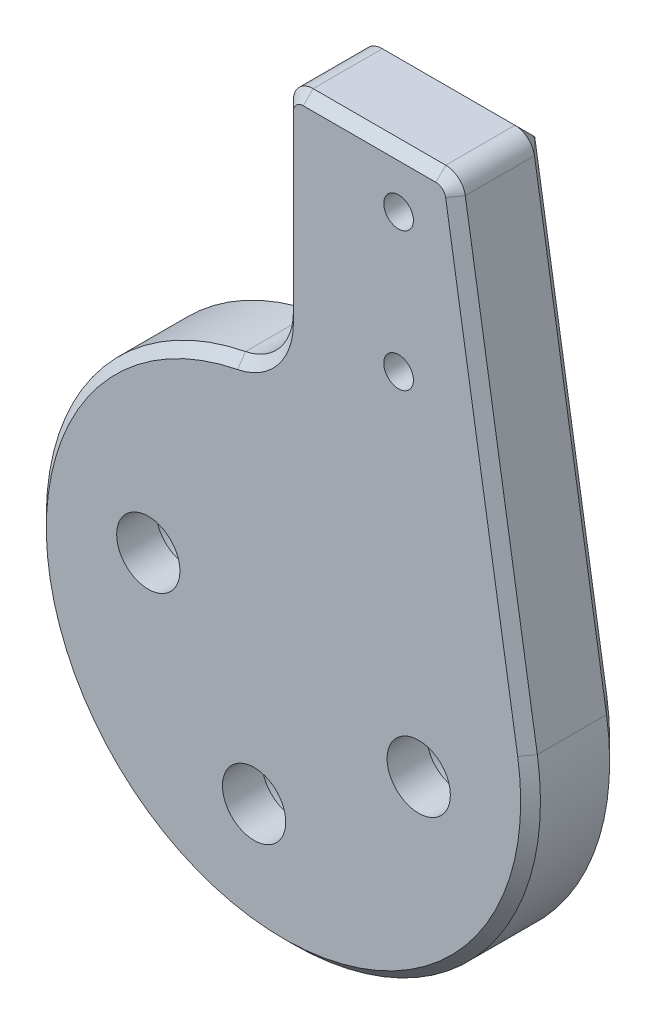
SolidWorks part; units mm, degrees
ref_plane "Front Plane" through (0, 0, 0) normal (0, 0, 1) x (1, 0, 0)
ref_plane "Top Plane" through (0, 0, 0) normal (0, 1, 0) x (1, 0, 0)
ref_plane "Right Plane" through (0, 0, 0) normal (1, 0, 0) x (0, 0, -1)
sketch "Sketch1" plane through (0, 0, 0) normal (0, 0, 1) x (1, 0, 0)
  line L0 (0, 0) -> (0, 11.5555) construction
  line L1 (0.5606, 13) -> (0.01, 13)
  line L2 (0.5606, 13) -> (0.5606, 25.4916) construction
  line L3 (0.5606, 13) -> (6.8007, 13) construction
  line L4 (6.8007, 13) -> (6.8007, 25.4916) construction
  line L5 (0.5606, 25.4916) -> (6.8007, 25.4916) construction
  line L6 (-3.2532, 27.1421) -> (0.01, 13) construction
  line L7 (1, 25.4916) -> (7.7086, 25.4916)
  line L8 (8.6959, 24.6504) -> (12.3414, 1.985)
  line L9 (0.5606, 25.4916) -> (0, 25.4916)
  line L10 (0, 24.4916) -> (0, 15.2069)
  line L11 (0, 12.5) -> (0, 30.616) construction
  arc A0 (-2.4194, 12.2636) -> (12.3414, 1.985) centre (0, 0) ccw
  circle A1 centre (-6.8401, 1.4875) radius 1.6
  circle A2 centre (-1.4875, -6.8401) radius 1.6
  circle A3 centre (6.8401, -1.4875) radius 1.6
  circle A4 centre (5.8209, 15.75) radius 0.75
  circle A5 centre (5.8209, 22.75) radius 0.75
  arc A6 (0, 24.4916) -> (1, 25.4916) centre (1, 24.4916) cw
  arc A7 (7.7086, 25.4916) -> (8.6959, 24.6504) centre (7.7086, 24.4916) cw
  arc A8 (-2.4194, 12.2636) -> (0, 15.2069) centre (-3, 15.2069) ccw
  dimension "D3" = 1.5
  dimension "D5" = 1
  dimension "D6" = 3
  dimension "D7" = 3.2
  dimension "D1" = 13
  dimension "D2" = 2.75
  dimension "D4" = 7
extrude "Boss-Extrude1" add sketch "Sketch1" along normal blind 5 contours A8 A0 L8 A7 L7 A6 L10 A5 A4 A3 A2 A1 region at (1.2908, 4.2009, 0)
chamfer "Chamfer1" distance 1 angle 45 7 edges at (-0.6825, 13.3019, 5) (-7.1431, -10.258, 5) (0, 19.8493, 5) (10.5187, 13.3177, 5) (0.2929, 25.1987, 5) (8.3571, 25.2528, 5) (4.3543, 25.4916, 5)
chamfer "Chamfer2" distance 0.5 angle 45 2 edges at (6.5709, 15.75, 5) (6.5709, 22.75, 5)
sketch "Sketch2" plane through (0, 0, 5) normal (0, 0, 1) x (1, 0, 0)
  circle A0 centre (-6.8401, 1.4875) radius 2.8
  circle A1 centre (-1.4875, -6.8401) radius 2.8
  circle A2 centre (6.8401, -1.4875) radius 2.8
  dimension "D1" = 5.6
extrude "Cut-Extrude1" cut sketch "Sketch2" against normal blind 3
chamfer "Chamfer3" distance 0.5 angle 45 7 edges at (-0.6825, 13.3019, 0) (-7.1431, -10.258, 0) (0, 19.8493, 0) (10.5187, 13.3177, 0) (0.2929, 25.1987, 0) (8.3571, 25.2528, 0) (4.3543, 25.4916, 0)
mirror "Mirror1" about plane through (0, 0, 0) normal (0, 0, 1) of "Chamfer3", "Boss-Extrude1", "Chamfer1", "Cut-Extrude1"
sketch "Sketch3" plane through (0, 0, 5) normal (0, 0, 1) x (1, 0, 0)
  circle A0 centre (0, 0) radius 37.3425
extrude "Cut-Extrude2" cut sketch "Sketch3" against normal blind 5 contours A0
